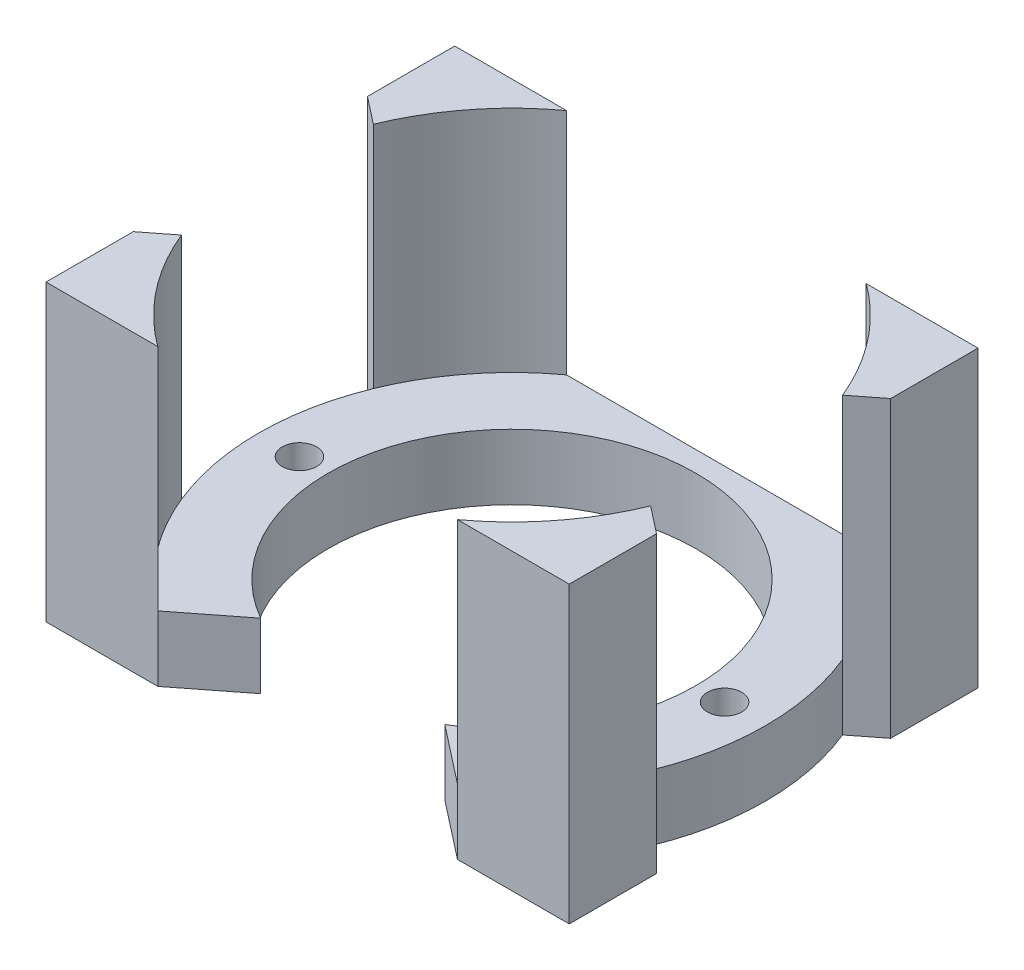
SolidWorks part; units mm, degrees
ref_plane "Front Plane" through (0, 0, 0) normal (0, 0, 1) x (1, 0, 0)
ref_plane "Top Plane" through (0, 0, 0) normal (0, 1, 0) x (1, 0, 0)
ref_plane "Right Plane" through (0, 0, 0) normal (1, 0, 0) x (0, 0, -1)
sketch "Sketch1" plane through (0, 0, 0) normal (0, 1, 0) x (1, 0, 0)
  line L0 (-32, 25) -> (32, -25) construction
  line L1 (32, -25) -> (-32, -25)
  line L2 (32, -25) -> (32, 25)
  line L3 (32, 25) -> (-32, 25)
  line L4 (-32, -25) -> (-32, 25)
  line L5 (0, 25) -> (0, -25) construction
  line L6 (32, 0) -> (-32, 0) construction
  line L7 (-32, -25) -> (32, 25) construction
  line L8 (-18.3303, 25) -> (-11.2626, 19.4783)
  line L9 (-28.6924, 11.7365) -> (-21.6247, 6.2148)
  line L10 (-32, -25) -> (-17.7305, -13.852)
  line L11 (18.3303, 25) -> (11.2626, 19.4783)
  line L12 (-11.2626, -19.4783) -> (-21.6379, -27.5841)
  line L13 (-28.6924, 11.7365) -> (-32, 14.3205)
  line L14 (-21.6247, -6.2148) -> (-32, -14.3205)
  line L15 (28.6924, 11.7365) -> (21.6247, 6.2148)
  line L16 (21.6247, -6.2148) -> (32, -14.3205)
  line L17 (11.2626, -19.4783) -> (21.6379, -27.5841)
  line L18 (28.6924, 11.7365) -> (32, 14.3205)
  circle A0 centre (0, 0) radius 22.5
  circle A1 centre (0, 0) radius 31
  circle A2 centre (-26, 0) radius 2.1
  circle A3 centre (26, 0) radius 2.1
  dimension "D1" = 45
  dimension "D2" = 62
  dimension "D5" = 4.2
  dimension "D3" = 64
  dimension "D4" = 50
  dimension "D6" = 26
extrude "Boss-Extrude1" add sketch "Sketch1" along normal blind 8 contours L8 A1 L9 A0 | A0 L11 L3 L8 | L15 A1 L11 A0 | L16 A1 L15 A0 | L17 A1 L16 A0 | L10 A1 L12 A0 | L14 A1 L10 A0 | L9 A1 L14 A0 | A1 L3 L4 L13 | A1 L18 L2 L3 | A1 L1 L2 L16 | A1 L10 L1 | A1 L14 L4 L10 region at (27.5253, 0, 20.1834) region at (20.7114, 0, 16.1808) region at (-18.0979, 0, 19.5261) region at (-25.0676, 0, 23.0669) region at (25.3141, 0, 8.7765) region at (27.5253, 0, -20.1834) region at (-29.2139, 0, 18.2023) region at (-23.325, 0, 12.8355) region at (20.7114, 0, -16.1808) region at (-30.7472, 0, 0) region at (0, 0, -23.1509) region at (-27.5253, 0, -20.1834) region at (-20.7114, 0, -16.1808)
extrude "Boss-Extrude2" add sketch "Sketch1<4>" along normal blind 36 contours A1 L18 L2 L3 | A1 L3 L4 L13 | A1 L14 L4 L10 | A1 L10 L1 | A1 L1 L2 L16 region at (27.5253, 0, 20.1834) region at (-25.0676, 0, 23.0669) region at (27.5253, 0, -20.1834) region at (-29.2139, 0, 18.2023) region at (-27.5253, 0, -20.1834)
sketch "Sketch1<4>" plane through (0, 0, 0) normal (0, 1, 0) x (1, 0, 0) same geometry as "Sketch1"
